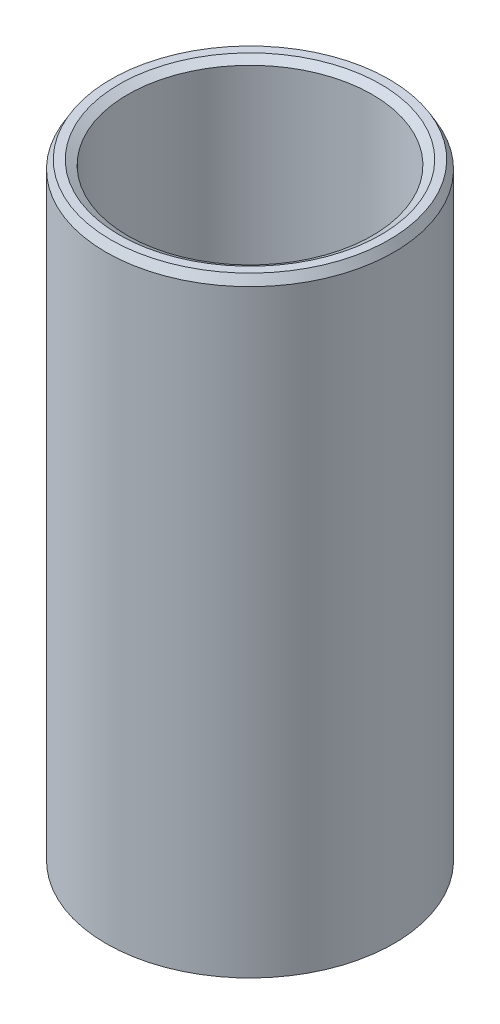
SolidWorks part; units mm, degrees
ref_plane "Front Plane" through (0, 0, 0) normal (0, 0, 1) x (1, 0, 0)
ref_plane "Top Plane" through (0, 0, 0) normal (0, 1, 0) x (1, 0, 0)
ref_plane "Right Plane" through (0, 0, 0) normal (1, 0, 0) x (0, 0, -1)
sketch "Sketch1" plane through (0, 0, 0) normal (0, 1, 0) x (1, 0, 0)
  circle A0 centre (0, 0) radius 55
  dimension "SLEEVE_OD" = 110
extrude "Boss-Extrude1" add sketch "Sketch1" along normal blind 233.8283
sketch "Sketch2" plane through (0, 0, 0) normal (0, 1, 0) x (1, 0, 0)
  circle A0 centre (0, 0) radius 46.733
  dimension "BORE_D" = 93.4659
extrude "Cut-Extrude1" cut sketch "Sketch2" along normal through all
chamfer "Chamfer1" distance 3.1905 angle 30 4 edges at (0, 233.8283, 46.733) (0, 0, 46.733) (0, 0, 55) (0, 233.8283, 55) first distance on face at (0, 233.8283, 46.733) first distance on face at (0, 0, 46.733) first distance on face at (0, 233.8283, 55)
